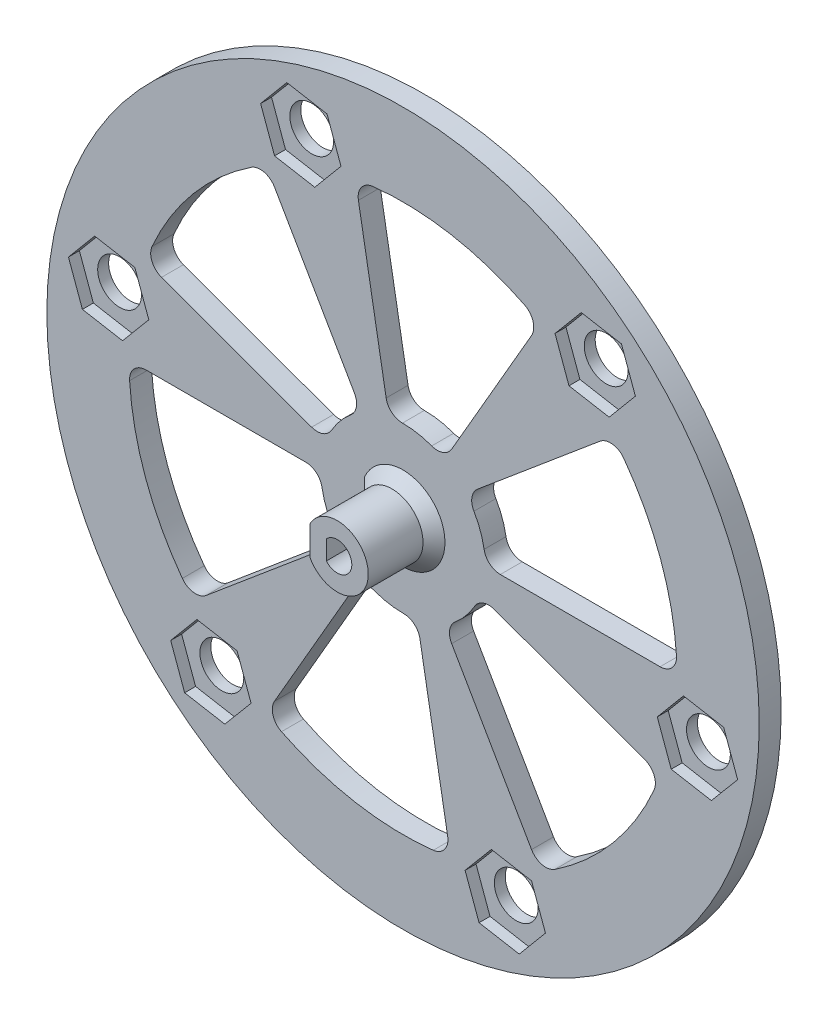
SolidWorks part; units mm, degrees
ref_plane "Plan de face" through (0, 0, 0) normal (0, 0, 1) x (1, 0, 0)
ref_plane "Plan de dessus" through (0, 0, 0) normal (0, 1, 0) x (1, 0, 0)
ref_plane "Plan de droite" through (0, 0, 0) normal (1, 0, 0) x (0, 0, -1)
sketch "Esquisse1" plane through (0, 0, 0) normal (0, 0, 1) x (1, 0, 0)
  circle A0 centre (0, 0) radius 65
  dimension "D1" = 130
extrude "Boss.-Extru.1" add sketch "Esquisse1" along normal blind 4
sketch "Esquisse2" plane through (0, 0, 4) normal (0, 0, 1) x (1, 0, 0)
  line L0 (-2, 1.7385) -> (-2, -1.7385)
  arc A0 (-2, 1.7385) -> (-2, -1.7385) centre (0, 0) cw
  point P5 (2.65, 0)
  dimension "D1" = 2.65
  dimension "D2" = 4.65
extrude "Enlèv. mat.-Extru.1" cut sketch "Esquisse2" against normal through all
sketch "Esquisse3" plane through (0, 0, 4) normal (0, 0, 1) x (1, 0, 0)
  line L0 (-2, 1.7385) -> (-2, -1.7385) construction
  line L1 (-2, 1.7385) -> (-2, -1.7385)
  line L2 (-5, 2.6311) -> (-5, -2.6311)
  arc A0 (-2, -1.7385) -> (-2, 1.7385) centre (0, 0) ccw construction
  arc A1 (-2, -1.7385) -> (-2, 1.7385) centre (0, 0) ccw
  arc A2 (-5, -2.6311) -> (-5, 2.6311) centre (0, 0) ccw
  dimension "D1" = 3
extrude "Boss.-Extru.2" add sketch "Esquisse3" along normal blind 12
sketch "Esquisse4" plane through (-5, 0, 0) normal (-1, 0, 0) x (0, 0, 1)
  line L0 (16, 2.6311) -> (4, 2.6311) construction
  line L1 (16, 2.6311) -> (16, -2.6311) construction
  circle A0 centre (10, 0) radius 1.5
  point P5 (10, 2.6311)
  point P8 (16, 0)
  dimension "D1" = 3
extrude "Enlèv. mat.-Extru.2" cut sketch "Esquisse4" against normal up to next
chamfer "Chanfrein1" distance 2 angle 45 2 edges at (-5, 0, 4) (5.65, 0, 4)
sketch "Esquisse5" plane through (0, 0, 4) normal (0, 0, 1) x (1, 0, 0)
  line L0 (0, 0) -> (65, 0) construction
  line L1 (0, 0) -> (32.5, -56.2917) construction
  line L2 (0, 0) -> (61.08, -22.2313) construction
  line L3 (14.0954, -5.1303) -> (46.9846, -17.101)
  line L4 (7.5, -12.9904) -> (25, -43.3013)
  circle A0 centre (0, 0) radius 65 construction
  arc A1 (46.9846, -17.101) -> (25, -43.3013) centre (0, 0) cw
  arc A2 (14.0954, -5.1303) -> (7.5, -12.9904) centre (0, 0) cw
  dimension "D1" = 60
  dimension "D2" = 20
  dimension "D3" = 15
  dimension "D4" = 15
extrude "Enlèv. mat.-Extru.3" cut sketch "Esquisse5" against normal up to next
fillet "Congé1" radius 3 4 edges at (25, -43.3013, 2) (46.9846, -17.101, 2) (7.5, -12.9904, 2) (14.0954, -5.1303, 2)
sketch "Esquisse7" plane through (0, 0, 4) normal (0, 0, 1) x (1, 0, 0)
  line L0 (0, 0) -> (64.0125, -11.2871) construction
  line L1 (61.0581, -10.7662) -> (58.5108, -3.7675)
  line L2 (58.5108, -3.7675) -> (51.1761, -2.4742)
  line L3 (51.1761, -2.4742) -> (46.3887, -8.1796)
  line L4 (46.3887, -8.1796) -> (48.936, -15.1782)
  line L5 (48.936, -15.1782) -> (56.2707, -16.4715)
  line L6 (56.2707, -16.4715) -> (61.0581, -10.7662)
  line L7 (44.0755, -16.0422) -> (16.6779, -6.0703) construction
  circle A0 centre (53.7234, -9.4729) radius 6.45 construction
  circle A1 centre (0, 0) radius 65 construction
  dimension "D1" = 12.9
  dimension "D2" = 3
  dimension "D3" = 10
extrude "Enlèv. mat.-Extru.4" cut sketch "Esquisse7" against normal blind 2
sketch "Esquisse8" plane through (0, 0, 2) normal (0, 0, 1) x (1, 0, 0)
  line L0 (51.1761, -2.4742) -> (56.2707, -16.4715) construction
  circle A0 centre (53.7234, -9.4729) radius 4
  dimension "D1" = 8
extrude "Enlèv. mat.-Extru.5" cut sketch "Esquisse8" against normal up to next
ref_axis "Axe1" through (0, 0, -0.8) along (0, 0, 1)
pattern_circular "Répétition circulaire1" count 6 over 360 about axis through (0, 0, -0.8) along (0, 0, 1) of "Congé1", "Enlèv. mat.-Extru.3", "Enlèv. mat.-Extru.4", "Enlèv. mat.-Extru.5"
